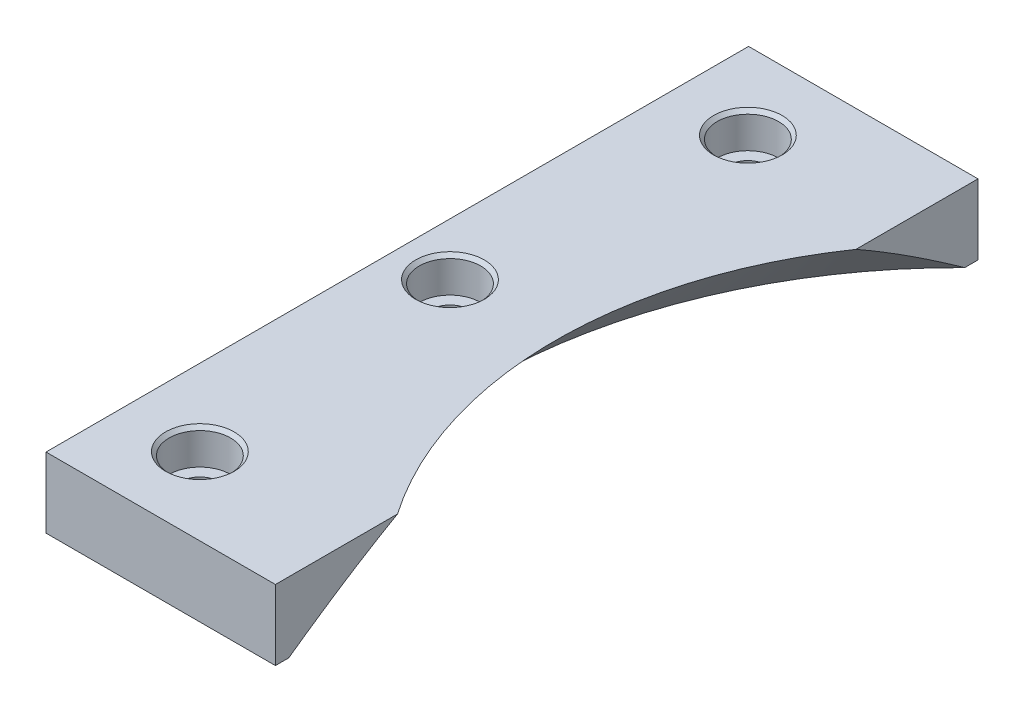
SolidWorks part; units mm, degrees
material "Malleable Cast Iron"
ref_plane "Front Plane" through (0, 0, 0) normal (0, 0, 1) x (1, 0, 0)
ref_plane "Top Plane" through (0, 0, 0) normal (0, 1, 0) x (1, 0, 0)
ref_plane "Right Plane" through (0, 0, 0) normal (1, 0, 0) x (0, 0, -1)
sketch "Sketch1" plane through (0, 0, 0) normal (0, 1, 0) x (1, 0, 0)
  line B0 (-101.6, 0) -> (-85.725, 0) construction
  line B1 (-87.757, 49.53) -> (-87.757, -49.53) construction
  line B2 (-101.6, 0) -> (101.6, 0) construction
  line B3 (-101.6, -63.5) -> (101.6, -63.5) construction
  line B4 (-101.6, -63.5) -> (-101.6, 63.5)
  line B5 (-101.6, 63.5) -> (101.6, 63.5) construction
  line B6 (0, 63.5) -> (0, -63.5) construction
  line B7 (-101.6, -63.5) -> (-57.5893, -63.5)
  line B8 (-101.6, 63.5) -> (-57.5893, 63.5)
  arc B9 (-57.5893, 63.5) -> (-57.5893, -63.5) centre (0, 0) ccw
sketch_block_instance "swivel blocks-1"
sketch_block "swivel blocks" parameters "D6"=171.45, "D1"=6.35, "D2"=2.032, "D3"=99.06, "D4"=203.2, "D5"=127
sketch "Sketch3" plane through (0, 0, 0) normal (0, 1, 0) x (1, 0, 0)
  line L0 (-101.6, -63.5) -> (-57.5893, -63.5) construction
  line L1 (-101.6, -63.5) -> (-101.6, 63.5) construction
  line L2 (-101.6, 63.5) -> (-57.5893, 63.5) construction
  line L3 (-101.6, -63.5) -> (-57.5893, -63.5)
  line L4 (-101.6, -63.5) -> (-101.6, 63.5)
  line L5 (-101.6, 63.5) -> (-57.5893, 63.5)
  arc A0 (-57.5893, 63.5) -> (-57.5893, -63.5) centre (0, 0) ccw construction
  arc A1 (-57.5893, 63.5) -> (-57.5893, -63.5) centre (0, 0) ccw
extrude "Boss-Extrude3" add sketch "Sketch3" along normal blind 12.7
draft "Draft1" type of draft neutral plane draft angle 45 neutral plane "Top Plane" faces to draft 1 face at (-71.6571, 6.35, 0) neutral plane through (0, 0, 0) neutral plane normal (0, 1, 0) reverse direction yes parameters "D1"=45
sketch "Sketch4" plane through (0, 0, 0) normal (0, 1, 0) x (1, 0, 0)
  line L1 (0, 63.5) -> (-60.1293, 63.5)
  line L2 (0, 63.5) -> (0, -63.5)
  line L3 (0, -63.5) -> (-60.1293, -63.5)
  line L4 (-60.1293, 63.5) -> (-60.1293, -63.5)
  dimension "D1" = 2.54
extrude "Cut-Extrude1" cut sketch "Sketch4" along normal through all
hole_wizard "CBORE for 1/4 Socket Head Cap Screw1" positions "Sketch7" profile "Sketch6" counterbore size "1/4" standard "ANSI Inch" end condition up to next
sketch "Sketch7" plane through (0, 12.7, 0) normal (0, 1, 0) x (1, 0, 0)
  point P7 (-87.757, 49.53)
  point P9 (-92.075, 0)
  point P11 (-87.757, -49.53)
sketch "Sketch6" plane through (-87.757, 12.7, -49.53) normal (1, 0, 0) x (0, 0, 1)
  line L0 (0, 0) -> (0, 12.7)
  line L1 (0, 12.7) -> (3.3782, 12.7)
  line L3 (3.3782, 12.7) -> (3.3782, 6.35)
  line L4 (5.5562, 6.35) -> (3.3782, 6.35)
  line L5 (5.5562, 6.35) -> (5.5562, 0.635)
  line L6 (5.5562, 0.635) -> (6.1913, 0)
  line L7 (6.1913, 0) -> (0, 0)
  line L8 (-5.5562, 0.635) -> (-6.1913, 0) construction
  line L11 (0, -6.35) -> (0, 107.95) construction
  dimension "Thru Hole Dia." = 6.7564
  dimension "Thru Hole Depth" = 12.7
  dimension "C'Bore Dia." = 11.1125
  dimension "C'Bore Depth" = 6.35
  dimension "Near C'Sink Dia." = 12.3825
  dimension "Near C'Sink Angle" = 90
equation "\"D6@swivel blocks\"=\"pressure-plate-OD\""
equation "\"D6@swivel blocks\"= \"pressure-plate-OD\""
equation "\"delta-z\" = 1.5"
equation "\"total-height\" = 3.28"
equation "\"mid-height\" = 1.5"
equation "\"jaw-width\" = 4"
equation "\"jaw-height\" = \"total-height\" - \"mid-height\""
equation "\"max-tube-diam\" = 3.5"
equation "\"v-block-notch-height\" = 1.5"
equation "\"v-block-notch-angle\" = 120"
equation "\"jaw-mod-plate-thickness\" = .375"
equation "\"jaw-mod-plate-extension-thickness\" = .15"
equation "\"jaw-mod-height\" =  \"max-tube-diam\"/2 + \"delta-z\" + \"v-block-notch-height\"/2"
equation "\"jaw-travel\" = 4.45"
equation "\"rib-top-width\" = 0.5"
equation "\"rib-side-width\" = 0.5"
equation "\"quarter-twenty-close-clearance\" = .257"
equation "\"box-way-width\" = 1.5"
equation "\"box-way-depth\" = 1.5"
equation "\"screw-OD\" = .625"
equation "\"screw-reduced-diam\" = .47"
equation "\"pressure-plate-OD\" = 6.75"
equation "\"swivel-cleat-thick\" = .5"
equation "\"swivel-gap\" = .02"
equation "\"D1@Boss-Extrude3\"=\"swivel-cleat-thick\""
